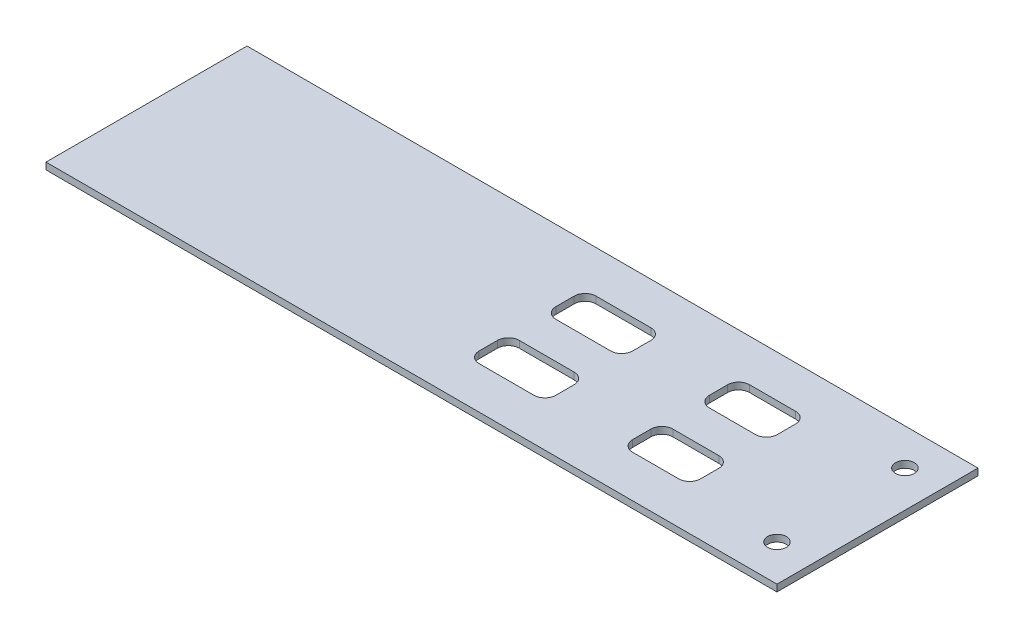
SolidWorks part; units mm, degrees
ref_plane "Front Plane" through (0, 0, 0) normal (0, 0, 1) x (1, 0, 0)
ref_plane "Top Plane" through (0, 0, 0) normal (0, 1, 0) x (1, 0, 0)
ref_plane "Right Plane" through (0, 0, 0) normal (1, 0, 0) x (0, 0, -1)
sketch "Sketch1" plane through (0, 0, 0) normal (0, 1, 0) x (1, 0, 0)
  line L1 (0, 0) -> (152.4, 0)
  line L2 (0, 0) -> (0, 69.85)
  line L3 (0, 69.85) -> (152.4, 69.85)
  line L4 (152.4, 0) -> (152.4, 69.85)
  dimension "D1" = 69.85
  dimension "D2" = 152.4
extrude "Boss-Extrude1" add sketch "Sketch1" along normal blind 2.3622
sketch "Sketch2" plane through (0, 2.3622, 0) normal (0, 1, 0) x (1, 0, 0)
  line L0 (0, 69.85) -> (0, 0) construction
  line L1 (30.48, 55.245) -> (57.15, 55.245)
  line L2 (30.48, 55.245) -> (30.48, 41.275)
  line L3 (30.48, 41.275) -> (57.15, 41.275)
  line L4 (57.15, 55.245) -> (57.15, 41.275)
  line L5 (83.82, 55.245) -> (107.442, 55.245)
  line L6 (83.82, 55.245) -> (83.82, 41.275)
  line L7 (83.82, 41.275) -> (107.442, 41.275)
  line L8 (107.442, 55.245) -> (107.442, 41.275)
  line L9 (152.4, 0) -> (152.4, 69.85) construction
  line L10 (30.48, 28.575) -> (57.15, 28.575)
  line L11 (30.48, 28.575) -> (30.48, 14.605)
  line L12 (30.48, 14.605) -> (57.15, 14.605)
  line L13 (57.15, 28.575) -> (57.15, 14.605)
  line L14 (83.82, 28.575) -> (107.442, 28.575)
  line L15 (83.82, 28.575) -> (83.82, 14.605)
  line L16 (83.82, 14.605) -> (107.442, 14.605)
  line L17 (107.442, 28.575) -> (107.442, 14.605)
  point P10 (83.82, 48.26)
  point P17 (0, 34.925)
  dimension "D1" = 26.67
  dimension "D2" = 23.622
  dimension "D3" = 44.958
  dimension "D4" = 13.97
  dimension "D5" = 12.7
  dimension "D6" = 6.35
  dimension "D7" = 30.48
extrude "Cut-Extrude1" cut sketch "Sketch2" against normal through all
fillet "Fillet1" radius 3.81 16 edges at (83.82, 1.1811, -14.605) (83.82, 1.1811, -41.275) (30.48, 1.1811, -41.275) (30.48, 1.1811, -14.605) (107.442, 1.1811, -14.605) (57.15, 1.1811, -41.275) (57.15, 1.1811, -14.605) (107.442, 1.1811, -41.275) (107.442, 1.1811, -28.575) (107.442, 1.1811, -55.245) (57.15, 1.1811, -28.575) (57.15, 1.1811, -55.245) (30.48, 1.1811, -28.575) (83.82, 1.1811, -28.575) (83.82, 1.1811, -55.245) (30.48, 1.1811, -55.245)
sketch "Sketch4" plane through (0, 0, 0) normal (-1, 0, 0) x (0, 0, 1)
  line L1 (-69.85, 2.3622) -> (0, 2.3622)
  line L2 (-69.85, 2.3622) -> (-69.85, 0)
  line L3 (-69.85, 0) -> (0, 0)
  line L4 (0, 2.3622) -> (0, 0)
extrude "Boss-Extrude2" add sketch "Sketch4" along normal blind 101.6
sketch "Sketch5" plane through (0, 0, 0) normal (0, -1, 0) x (1, 0, 0)
  line L0 (152.4, 0) -> (152.4, -69.85) construction
  line L1 (-101.6, 0) -> (152.4, 0) construction
  line L2 (152.4, -69.85) -> (-101.6, -69.85) construction
  circle A0 centre (139.7, -12.7) radius 3.2639
  circle A1 centre (139.7, -57.15) radius 3.2639
  point P6 (0, 0)
  dimension "D1" = 6.5278
  dimension "D2" = 12.7
  dimension "D3" = 12.7
  dimension "D4" = 12.7
extrude "Cut-Extrude2" cut sketch "Sketch5" against normal through all
